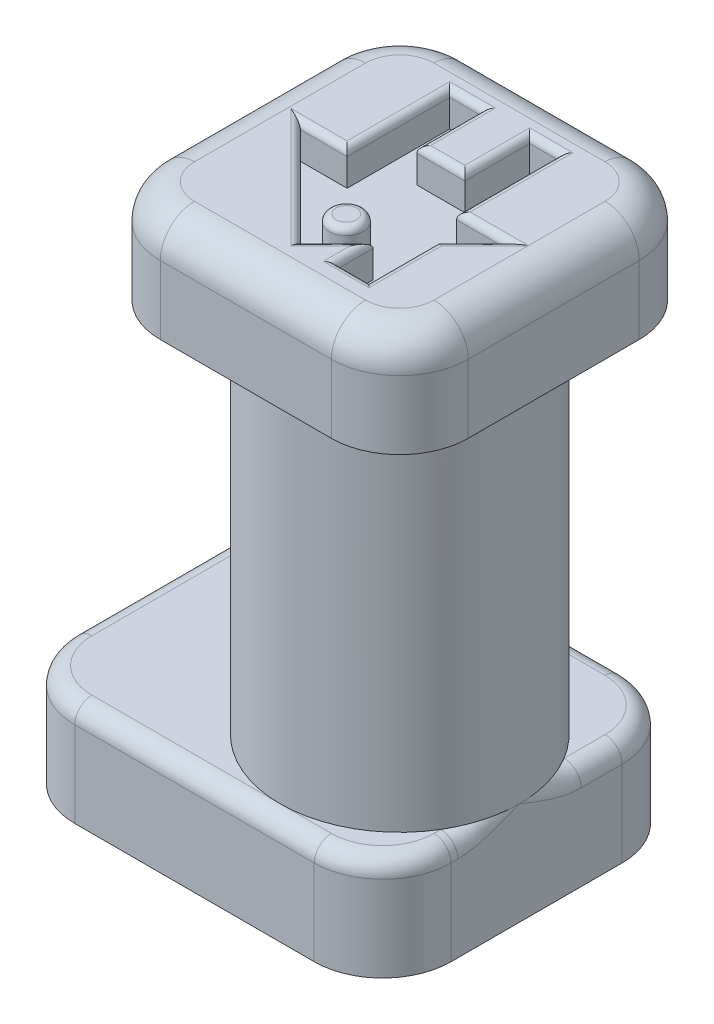
SolidWorks part; units mm, degrees
ref_plane "Спереди" through (0, 0, 0) normal (0, 0, 1) x (1, 0, 0)
ref_plane "Сверху" through (0, 0, 0) normal (0, 1, 0) x (1, 0, 0)
ref_plane "Справа" through (0, 0, 0) normal (1, 0, 0) x (0, 0, -1)
sketch "Эскиз1" plane through (0, 0, 0) normal (0, 1, 0) x (1, 0, 0)
  line L0 (-2.5, 3.5) -> (2.5, 3.5)
  line L1 (-2.5, -5.5) -> (2.5, -5.5)
  line L6 (4.5, -1002.5) -> (4.5, 48997.5) construction
  line L7 (-4.5, -1002.5) -> (-4.5, 48997.5) construction
  line L8 (-4.5, 1.5) -> (-4.5, -3.5)
  line L9 (-1004.5, 1.5) -> (48995.5, 1.5) construction
  line L10 (-1004.5, -3.5) -> (48995.5, -3.5) construction
  line L11 (4.5, -3.5) -> (4.5, 1.5)
  arc A4 (-2.5, 3.5) -> (-4.5, 1.5) centre (-2.5, 1.5) ccw
  arc A5 (2.5, 3.5) -> (4.5, 1.5) centre (2.5, 1.5) cw
  arc A6 (4.5, -3.5) -> (2.5, -5.5) centre (2.5, -3.5) cw
  arc A7 (-2.5, -5.5) -> (-4.5, -3.5) centre (-2.5, -3.5) cw
  point P4 (4.5, -1000)
  point P6 (4.5, 49000)
  point P7 (-4.5, -1000)
  point P8 (-4.5, 49000)
  point P9 (-1000, -4.5)
  point P10 (49000, -4.5)
  point P11 (-1000, 4.5)
  point P12 (49000, 4.5)
extrude "Бобышка-Вытянуть1" add sketch "Эскиз1" along normal blind 3
fillet "Скругление1" radius 1 8 edges at (-4.5, 3, 1) (-3.9142, 3, 4.9142) (0, 3, 5.5) (3.9142, 3, 4.9142) (-3.9142, 3, -2.9142) (0, 3, -3.5) (3.9142, 3, -2.9142) (4.5, 3, 1)
sketch "Эскиз2" plane through (0, 0, 0) normal (0, -1, 0) x (1, 0, 0)
  line L0 (-1000, 0) -> (49000, 0) construction
  line L1 (-1000, 1) -> (49000, 1) construction
  line L2 (0, -1000) -> (0, 49000) construction
  circle A1 centre (0, 1) radius 3.5
  dimension "D1" = 1
extrude "Бобышка-Вытянуть2" add sketch "Эскиз2" along normal blind 16
sketch "Эскиз3" plane through (0, 3, 0) normal (0, 1, 0) x (1, 0, 0)
  line L0 (0.7381, 2.0598) -> (0.7381, 0.1629)
  line L1 (0.0381, -3.9402) -> (-2.9619, -0.9402)
  line L2 (0.0381, -3.9402) -> (1.1, -2.8783)
  line L6 (-0.9619, 2.0598) -> (-0.6619, 2.0598)
  line L7 (1.0381, 2.0598) -> (1.6, 2.0598)
  line L8 (1.6, 2.0598) -> (1.6, -0.9402)
  line L9 (1.6, -0.9402) -> (3.0381, -0.9402)
  line L16 (-0.9619, 2.0598) -> (-1.6, 2.0598)
  line L20 (-1.6, 2.0598) -> (-1.6, -0.9402)
  line L25 (-1.6, -0.9402) -> (-2.9619, -0.9402)
  line L26 (0.7381, 0.1629) -> (-0.6619, 0.1629)
  line L27 (-0.6619, 0.1629) -> (-0.6619, 2.0598)
  line L28 (0.7381, 2.0598) -> (1.0381, 2.0598)
  line L29 (2.0381, -1.9402) -> (2.0381, -3.9402)
  line L30 (2.0381, -3.9402) -> (1.1, -3.9402)
  line L31 (1.1, -3.9402) -> (1.1, -2.8783)
  line L32 (2.0381, -1.9402) -> (3.0381, -0.9402)
  circle A0 centre (0.0381, -2.5994) radius 0.4973
  point P7 (1, -1000)
  point P10 (1, 49000)
  point P11 (-1, -1000)
  point P12 (-1, 49000)
extrude "Вырез-Вытянуть1" cut sketch "Эскиз3" against normal blind 1
fillet "Скругление2" radius 0.2 16 edges at (1.1, 3, 3.4092) (1.569, 3, 3.9402) (2.0381, 3, 2.9402) (2.5381, 3, 1.4402) (2.319, 3, 0.9402) (1.6, 3, -0.5598) (1.169, 3, -2.0598) (0.7381, 3, -1.1113) (0.0381, 3, -0.1629) (-0.6619, 3, -1.1113) (-1.131, 3, -2.0598) (-1.6, 3, -0.5598) (-2.281, 3, 0.9402) (-1.4619, 3, 2.4402) (0.569, 3, 3.4092) (0.0381, 3, 3.0967)
sketch "Эскиз6" plane through (0, -16, 0) normal (0, -1, 0) x (1, 0, 0)
  line L0 (-1000, 0) -> (49000, 0) construction
  line L1 (-1002, 1) -> (48998, 1) construction
  line L2 (-2, -1000) -> (-2, 49000) construction
  line L4 (-1001.3554, -4.5) -> (48998.6446, -4.5) construction
  circle A6 centre (-2, 0) radius 3.75
sketch "Эскиз7" plane through (0, -16, 0) normal (0, -1, 0) x (1, 0, 0)
  line L0 (-1000, -3.5) -> (49000, -3.5) construction
  line L1 (-5.5, -4) -> (1.5, -4)
  line L2 (3.5, -1000) -> (3.5, 49000) construction
  line L4 (-7.5, -994.5) -> (-7.5, 49005.5) construction
  line L5 (-1002, 5) -> (48998, 5) construction
  line L6 (-5.5, -998) -> (-5.5, 49002) construction
  line L7 (-7.5, 3) -> (-7.5, -2)
  line L11 (3.5, 3) -> (3.5, -2)
  line L12 (-5.5, 5) -> (1.5, 5)
  line L14 (-1007.5, -2) -> (48992.5, -2) construction
  line L15 (-1002, 3) -> (48998, 3) construction
  arc A1 (-5.5, -4) -> (-7.5, -2) centre (-5.5, -2) cw
  arc A2 (3.5, -2) -> (1.5, -4) centre (1.5, -2) cw
  arc A4 (-5.5, 5) -> (-7.5, 3) centre (-5.5, 3) ccw
  arc A5 (1.5, 5) -> (3.5, 3) centre (1.5, 3) cw
  point P7 (-1002, 7.5)
  point P9 (48998, 7.5)
  point P10 (-7.5, -998)
  point P11 (-7.5, 49002)
  point P21 (3.5, -3.5)
  point P24 (3.5, 7.5)
  dimension "D2" = 2
extrude "Бобышка-Вытянуть3" add sketch "Эскиз7" against normal blind 5
extrude "Вырез-Вытянуть2" cut sketch "Эскиз6" against normal blind 4 rebuild error yes
fillet "Скругление3" radius 0.5 9 edges at (3.5, -11, -0.5) (3.5, -11, 2) (2.9142, -11, -3.4142) (-2, -11, -4) (-6.9142, -11, -3.4142) (-7.5, -11, 0.5) (-6.9142, -11, 4.4142) (-2, -11, 5) (2.9142, -11, 4.4142)
sketch "Эскиз8" plane through (0, -16, 0) normal (0, -1, 0) x (1, 0, 0)
  line L1 (4.6164, 8.2931) -> (-8.6164, 8.2931)
  line L2 (4.6164, 8.2931) -> (4.6164, -4.2931)
  line L3 (4.6164, -4.2931) -> (-8.6164, -4.2931)
  line L4 (-8.6164, 8.2931) -> (-8.6164, -4.2931)
  line L5 (4.6164, 8.2931) -> (-8.6164, -4.2931) construction
  line L6 (4.6164, -4.2931) -> (-8.6164, 8.2931) construction
  point P0 (-2, 2)
extrude "Вырез-Вытянуть3" cut sketch "Эскиз8" against normal blind 2
sketch "Эскиз9" plane through (0, 0, 0) normal (0, 1, 0) x (1, 0, 0)
  line L0 (-1003.8653, -4.5) -> (48996.1347, -4.5) construction
  line L2 (-999.6562, -3.5) -> (49000.3438, -3.5) construction
extrude "Вырез-Вытянуть4" cut sketch "Эскиз6<5>" against normal blind 4
sketch "Эскиз6<5>" plane through (0, -16, 0) normal (0, -1, 0) x (1, 0, 0) same geometry as "Эскиз6"
